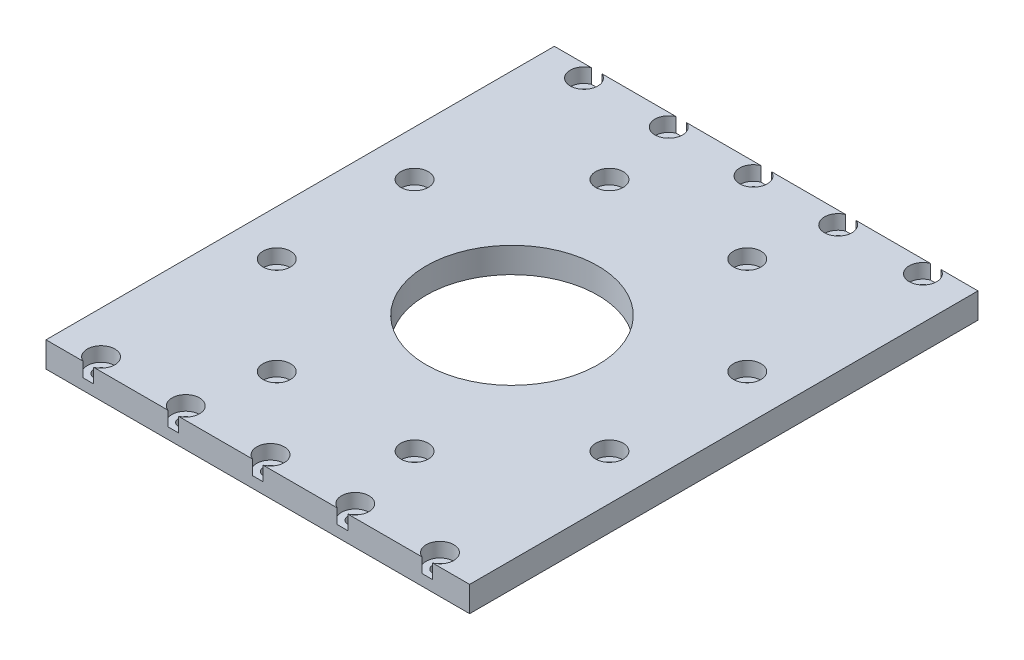
SolidWorks part; units mm, degrees
material "6061-T6 (SS)"
ref_plane "Front Plane" through (0, 0, 0) normal (0, 0, 1) x (1, 0, 0)
ref_plane "Top Plane" through (0, 0, 0) normal (0, 1, 0) x (1, 0, 0)
ref_plane "Right Plane" through (0, 0, 0) normal (1, 0, 0) x (0, 0, -1)
sketch "Sketch1" plane through (0, 0, 0) normal (0, 1, 0) x (1, 0, 0)
  circle A0 centre (0, 0) radius 50
  circle A1 centre (0, 0) radius 20.25
  dimension "D1" = 100
  dimension "D2" = 40.5
extrude "Boss-Extrude1" add sketch "Sketch1" along normal blind 6
sketch "Sketch2" plane through (0, 6, 0) normal (0, 1, 0) x (1, 0, 0)
  line L0 (-16.264, 39.2649) -> (16.264, 39.2649) construction
  circle A0 centre (0, 0) radius 42.5 construction
  point P4 (-16.264, 39.2649)
  point P10 (16.264, 39.2649)
  point P11 (39.2649, 16.264)
  point P12 (39.2649, -16.264)
  point P13 (16.264, -39.2649)
  point P14 (-16.264, -39.2649)
  point P15 (-39.2649, -16.264)
  point P16 (-39.2649, 16.264)
  dimension "D1" = 85
  dimension "D2" = 8
hole_wizard "CBORE for M3 Hex Socket Head Cap Screw2" positions "Sketch2" profile "Sketch3" counterbore size "M3" standard "DIN" end condition through all
sketch "Sketch3" plane through (-39.2649, 6, -16.264) normal (1, 0, 0) x (0, 0, 1)
  line L0 (0, 0) -> (0, 6)
  line L1 (0, 6) -> (1.7, 6)
  line L3 (1.7, 6) -> (1.7, 3.4)
  line L4 (1.7, 3.4) -> (3.25, 3.4)
  line L5 (3.25, 3.4) -> (3.25, 0)
  line L7 (3.25, 0) -> (0, 0)
  line L11 (0, -6.35) -> (0, 107.95) construction
  dimension "Thru Hole Dia." = 3.4
  dimension "Thru Hole Depth" = 6
  dimension "C'Bore Dia." = 6.5
  dimension "C'Bore Depth" = 3.4
sketch "Sketch6" plane through (0, 6, 0) normal (0, 1, 0) x (1, 0, 0)
  line L0 (-50, 0) -> (-50, -60)
  line L1 (-50, -60) -> (50, -60)
  line L2 (50, -60) -> (50, 0)
  circle A0 centre (0, 0) radius 50 construction
  arc A1 (-50, 0) -> (50, 0) centre (0, 0) ccw
  dimension "D1" = 60
extrude "Boss-Extrude2" add sketch "Sketch6" against normal up to surface (6 mm away) up to face at (-16.264, 0, -37.5649)
sketch "Sketch10" plane through (0, 6, 0) normal (0, 1, 0) x (1, 0, 0)
  line L0 (-50, 0) -> (-50, 60)
  line L1 (-50, 60) -> (50, 60)
  line L2 (50, 60) -> (50, 0)
  arc A0 (50, 0) -> (-50, 0) centre (0, 0) ccw construction
  arc A1 (50, 0) -> (-50, 0) centre (0, 0) ccw
  dimension "D1" = 60
extrude "Boss-Extrude3" add sketch "Sketch10" against normal up to surface (6 mm away) up to face at (-16.264, 0, -37.5649)
sketch "Sketch11" plane through (0, 6, 0) normal (0, 1, 0) x (1, 0, 0)
  line L0 (50, 60) -> (-50, 60) construction
  line L3 (0, 0) -> (0, 57) construction
  line L4 (0, 0) -> (-50000, 0) construction
  point P0 (-40, 57)
  point P13 (-20, 57)
  point P14 (0, 57)
  point P15 (20, 57)
  point P16 (40, 57)
  point P56 (0, 0)
  point P57 (40, -57)
  point P58 (20, -57)
  point P59 (0, -57)
  point P60 (-20, -57)
  point P61 (-40, -57)
  dimension "D1" = 3
  dimension "D2" = 5
  dimension "D5" = 20
hole_wizard "CBORE for M3 Hex Socket Head Cap Screw1" positions "Sketch11" profile "Sketch12" counterbore size "M3" standard "DIN" end condition through all
sketch "Sketch12" plane through (-40, 6, -57) normal (1, 0, 0) x (0, 0, 1)
  line L0 (0, 0) -> (0, 6)
  line L1 (0, 6) -> (1.7, 6)
  line L3 (1.7, 6) -> (1.7, 3.4)
  line L4 (1.7, 3.4) -> (3.25, 3.4)
  line L5 (3.25, 3.4) -> (3.25, 0)
  line L7 (3.25, 0) -> (0, 0)
  line L11 (0, -6.35) -> (0, 107.95) construction
  dimension "Thru Hole Dia." = 3.4
  dimension "Thru Hole Depth" = 6
  dimension "C'Bore Dia." = 6.5
  dimension "C'Bore Depth" = 3.4
